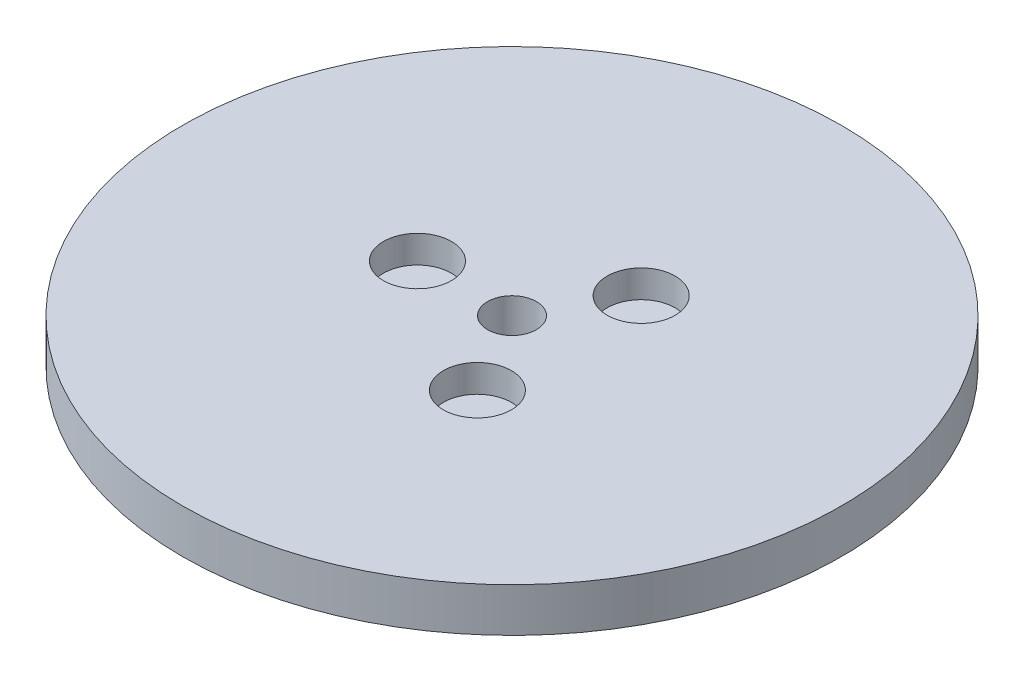
SolidWorks part; units mm, degrees
ref_plane "Front Plane" through (0, 0, 0) normal (0, 0, 1) x (1, 0, 0)
ref_plane "Top Plane" through (0, 0, 0) normal (0, 1, 0) x (1, 0, 0)
ref_plane "Right Plane" through (0, 0, 0) normal (1, 0, 0) x (0, 0, -1)
sketch "Sketch1" plane through (0, 0, 0) normal (0, 1, 0) x (1, 0, 0)
  circle A0 centre (0, 0) radius 67.5
  dimension "FLANGE_OD" = 135
extrude "Boss-Extrude1" add sketch "Sketch1" along normal blind 9
sketch "Sketch2" plane through (0, 0, 0) normal (0, 1, 0) x (1, 0, 0)
  circle A0 centre (0, 0) radius 5
  dimension "BORE_D" = 10
extrude "Cut-Extrude1" cut sketch "Sketch2" along normal through all
sketch "Sketch3" plane through (0, 9, 0) normal (0, 1, 0) x (1, 0, 0)
  circle A0 centre (0, 0) radius 19.3691 construction
  circle A1 centre (-19.3691, 0) radius 6.9631
  dimension "BOLT_D" = 13.9261
  dimension "BOLT_PCD" = 38.7383
extrude "Cut-Extrude2" cut sketch "Sketch3" against normal blind 5.6358
pattern_circular "CirPattern1" count 3 over 360 about axis through (0, 0, 0) along (0, 1, 0) of "Cut-Extrude2"
